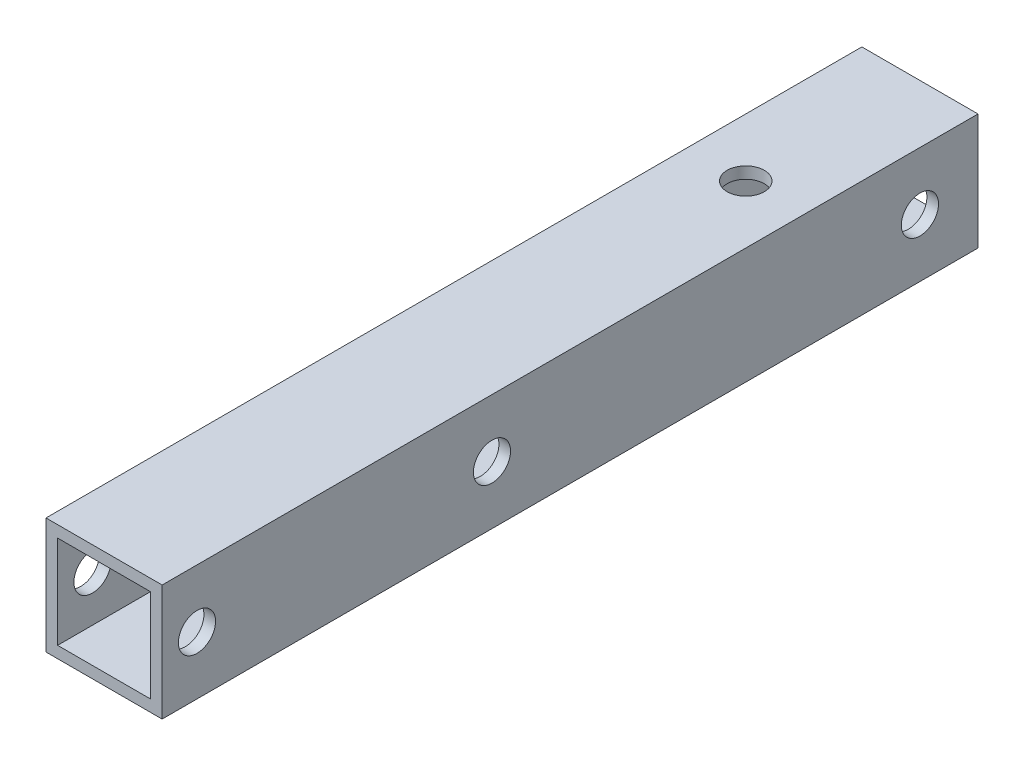
SolidWorks part; units mm, degrees
material "5052-H34"
ref_plane "正面" through (0, 0, 0) normal (0, 0, 1) x (1, 0, 0)
ref_plane "平面" through (0, 0, 0) normal (0, 1, 0) x (1, 0, 0)
ref_plane "右側面" through (0, 0, 0) normal (1, 0, 0) x (0, 0, -1)
sketch "ｽｹｯﾁ1" plane through (0, 0, 0) normal (0, 0, 1) x (1, 0, 0)
  line L1 (-5, 5) -> (5, 5)
  line L2 (-5, 5) -> (-5, -5)
  line L3 (-5, -5) -> (5, -5)
  line L4 (5, 5) -> (5, -5)
  line L5 (-5, 5) -> (5, -5) construction
  line L6 (-5, -5) -> (5, 5) construction
  point P0 (0, 0)
  dimension "D1" = 10
  dimension "D2" = 10
extrude "押し出し-薄板1" add sketch "ｽｹｯﾁ1" along normal blind 70.25 thin thin type one direction reverse wall 1
sketch "ｽｹｯﾁ2" plane through (0, 5, 0) normal (0, 1, 0) x (1, 0, 0)
  line L0 (0, 0) -> (0, -25) construction
  circle A1 centre (0, -15) radius 1.6
  dimension "D3" = 3.2
  dimension "D1" = 15
  dimension "D2" = 10
extrude "ｶｯﾄ - 押し出し1" cut sketch "ｽｹｯﾁ2" against normal through all
sketch "ｽｹｯﾁ3" plane through (5, 0, 0) normal (1, 0, 0) x (0, 0, -1)
  line L0 (-70.25, 0) -> (-41.85, 0) construction
  line L2 (0, 0) -> (-5, 0) construction
  line L3 (-70.25, -5) -> (-70.25, 5) construction
  line L4 (-70.25, -5) -> (0, -5) construction
  circle A0 centre (-41.85, 0) radius 1.6
  circle A1 centre (-67.25, 0) radius 1.6
  circle A2 centre (-5, 0) radius 1.6
  dimension "D1" = 3.2
  dimension "D2" = 25.4
  dimension "D3" = 3
  dimension "D4" = 5
  dimension "D5" = 5
extrude "ｶｯﾄ - 押し出し2" cut sketch "ｽｹｯﾁ3" against normal through all
